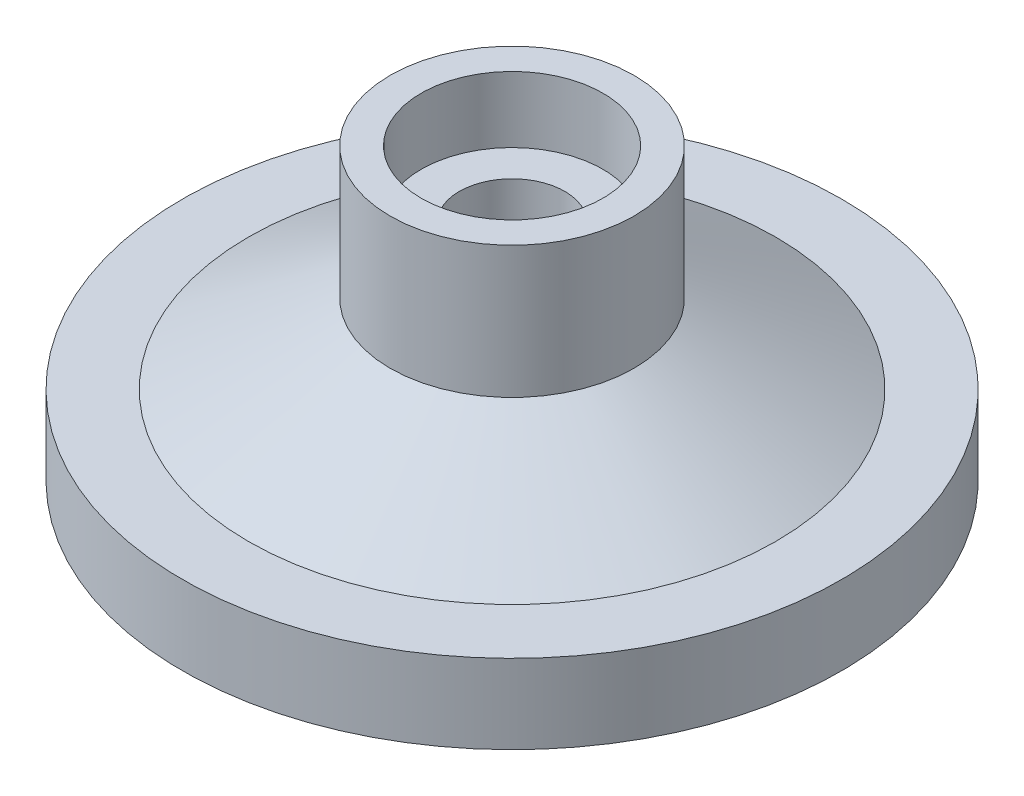
SolidWorks part; units mm, degrees
material "Cast Alloy Steel"
ref_plane "Front Plane" through (0, 0, 0) normal (0, 0, 1) x (1, 0, 0)
ref_plane "Top Plane" through (0, 0, 0) normal (0, 1, 0) x (1, 0, 0)
ref_plane "Right Plane" through (0, 0, 0) normal (1, 0, 0) x (0, 0, -1)
sketch "Sketch4" plane through (0, 0, 0) normal (0, 0, 1) x (1, 0, 0)
  line L0 (0, 0) -> (0, 17.8403) construction
  line L1 (0, 0) -> (25, 0) construction
  line L2 (25, 0) -> (25, 6)
  line L3 (25, 6) -> (20, 6)
  line L4 (9.25, 12) -> (20, 6)
  line L5 (9.25, 22) -> (0, 22)
  line L6 (9.25, 12) -> (9.25, 22)
  line L7 (25, 0) -> (0, 0)
  line L8 (0, 0) -> (0, 22)
  dimension "D1" = 5
  dimension "D2" = 25
  dimension "D3" = 9.25
revolve "Revolve1" add sketch "Sketch4" angle 360 about L8
sketch "Sketch5" plane through (0, 0, 0) normal (0, -1, 0) x (1, 0, 0)
  circle A0 centre (0, 0) radius 22
ref_plane "Plane1" through (0, 3, 0) normal (0, -1, 0) x (-1, 0, 0)
sketch "Sketch7" plane through (0, 3, 0) normal (0, -1, 0) x (-1, 0, 0)
  circle A0 centre (0, 0) radius 15
loft "Cut-Loft1" cut profiles "Sketch5", "Sketch7" connector at (-15.8755, 0, 15.2305) connector at (-10.986, 3, 10.2131)
sketch "Sketch8" plane through (0, 3, 0) normal (0, -1, 0) x (1, 0, 0)
  circle A0 centre (0, 0) radius 15
ref_plane "Plane2" through (0, 6, 0) normal (0, -1, 0) x (-1, 0, 0)
sketch "Sketch9" plane through (0, 6, 0) normal (0, -1, 0) x (-1, 0, 0)
  circle A0 centre (0, 0) radius 4
loft "Cut-Loft2" cut profiles "Sketch9", "Sketch8" connector at (-3.9997, 6, 0.0452) connector at (-14.2424, 3, 4.7069)
sketch "Sketch10" plane through (0, 6, 0) normal (0, -1, 0) x (1, 0, 0)
  circle A0 centre (0, 0) radius 4
extrude "Cut-Extrude1" cut sketch "Sketch10" against normal blind 20
sketch "Sketch11" plane through (0, 22, 0) normal (0, 1, 0) x (1, 0, 0)
  circle A0 centre (0, 0) radius 6.9
  dimension "D1" = 13.8
extrude "Cut-Extrude2" cut sketch "Sketch11" against normal blind 5
cosmetic thread "Cosmetic Thread1" parameters "D2"=16
